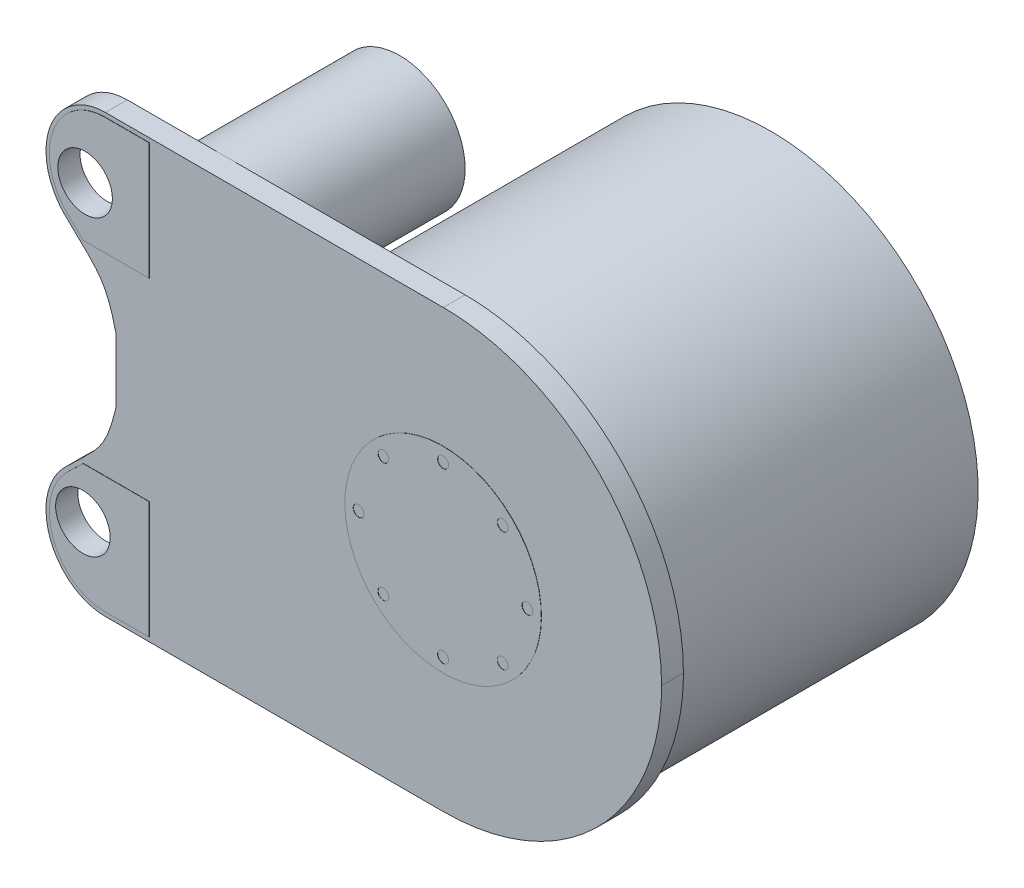
SolidWorks part; units mm, degrees
ref_plane "Plano frontal" through (0, 0, 0) normal (0, 0, 1) x (1, 0, 0)
ref_plane "Plano superior" through (0, 0, 0) normal (0, 1, 0) x (1, 0, 0)
ref_plane "Plano direito" through (0, 0, 0) normal (1, 0, 0) x (0, 0, -1)
sketch "Esboço1" plane through (0, 0, 0) normal (0, 0, 1) x (1, 0, 0)
  line L0 (-10.9, 1.5) -> (-10.9, 1.4998)
  line L1 (-10.9, -1.4998) -> (-10.9, -1.5)
  line L2 (-11.375, -9.9996) -> (-10.1, -9.9996)
  line L3 (-10.1, -9.9996) -> (4.1, -9.9996)
  line L4 (4.1, 9.9996) -> (-10.1, 9.9996)
  line L5 (-10.1, 9.9996) -> (-11.375, 9.9996)
  ellipse E0 centre (4.1, -0.0004) end of major axis (4.1, 9.4996) minor radius 9.5
  ellipse E1 centre (-12.3, 6.7497) end of major axis (-12.3, 7.9997) minor radius 1.25
  ellipse E2 centre (-12.4, -6.7497) end of major axis (-11.15, -6.7497) minor radius 1.2499
  ellipse E5 centre (4.1, -0.0004) end of major axis (4.1, 8.4996) minor radius 8.5
  spline S0 degree 3 poles (-11.375, 9.9996) (-12.8799, 9.9996) (-14.1, 8.7075) (-14.1, 7.1137) knots 0 0 0 0 0.05 0.05 0.05 0.05
  spline S1 degree 3 poles (-14.1, 7.1137) (-14.1, 6.3284) (-13.8037, 5.6164) (-13.3233, 5.0962) knots 0.05 0.05 0.05 0.05 0.1 0.1 0.1 0.1
  spline S2 degree 3 poles (-13.3233, 5.0962) (-13.3196, 5.092) (-13.3154, 5.0875) (-13.3114, 5.0835) knots 0.1 0.1 0.1 0.1 0.15 0.15 0.15 0.15
  spline S3 degree 3 poles (-13.3114, 5.0835) (-13.2765, 5.0461) (-13.2405, 5.0095) (-13.2036, 4.9741) knots 0.15 0.15 0.15 0.15 0.2 0.2 0.2 0.2
  spline S4 degree 3 poles (-13.2036, 4.9741) (-11.7596, 3.5417) (-11.3715, 3.4497) (-10.9, 1.5) knots 0.2 0.2 0.2 0.2 0.25 0.25 0.25 0.25
  spline S5 degree 3 poles (-10.9, 1.4998) (-10.9, 0.5) (-10.9, -0.5) (-10.9, -1.4998) knots 0.3 0.3 0.3 0.3 0.35 0.35 0.35 0.35
  spline S6 degree 3 poles (-10.9, -1.5) (-11.3712, -3.4492) (-11.761, -3.5431) (-13.2036, -4.9741) knots 0.4 0.4 0.4 0.4 0.45 0.45 0.45 0.45
  spline S7 degree 3 poles (-13.2036, -4.9741) (-13.2369, -5.006) (-13.2695, -5.0389) (-13.3011, -5.0725) knots 0.45 0.45 0.45 0.45 0.5 0.5 0.5 0.5
  spline S8 degree 3 poles (-13.3011, -5.0725) (-13.3105, -5.0824) (-13.3196, -5.0921) (-13.3287, -5.1021) knots 0.5 0.5 0.5 0.5 0.55 0.55 0.55 0.55
  spline S9 degree 3 poles (-13.3287, -5.1021) (-13.8059, -5.6217) (-14.1, -6.3313) (-14.1, -7.1137) knots 0.55 0.55 0.55 0.55 0.6 0.6 0.6 0.6
  spline S10 degree 3 poles (-14.1, -7.1137) (-14.1, -8.7075) (-12.8799, -9.9996) (-11.375, -9.9996) knots 0.6 0.6 0.6 0.6 0.65 0.65 0.65 0.65
  spline S11 degree 3 poles (4.1, -9.9996) (9.6228, -9.9996) (14.1, -5.5226) (14.1, 0) knots 0.75 0.75 0.75 0.75 0.8 0.8 0.8 0.8
  spline S12 degree 3 poles (14.1, 0) (14.1, 5.5226) (9.6228, 9.9996) (4.1, 9.9996) knots 0.8 0.8 0.8 0.8 0.85 0.85 0.85 0.85
  point P56 (-6.9, 6.9997)
  ellipse B0 centre (-6.9, 6.9997) end of major axis (-3.9, 6.9997) minor radius 2.9999
  ellipse B1 centre (-6.9, 6.9997) end of major axis (-9.15, 6.9997) minor radius 2.25
sketch_block_instance "Bloco1-1"
sketch_block "Bloco1"
extrude "Ressalto-extrusão1" add sketch "Esboço1" along normal blind 1 contours L4 L5 S0 S1 S2 S3 S4 L0 S5 L1 S6 S7 S8 S9 S10 L2 L3 S11 S12
ref_plane "Plano2" through (0, 0, 1) normal (0, 0, 1) x (1, 0, 0)
sketch "Esboço3" plane through (0, 0, 1) normal (0, 0, 1) x (1, 0, 0)
  line L0 (-12.3882, 4.4299) -> (-9.3652, 4.4299)
  line L1 (-9.3652, 4.4299) -> (-9.3652, 9.8065)
  line L2 (-9.3652, 9.8065) -> (-10.2039, 9.8065)
  line L3 (-10.2039, 9.8065) -> (-11.3935, 9.8065)
  line L4 (-12.3882, -4.4299) -> (-9.3652, -4.4299)
  line L5 (-9.3652, -4.4299) -> (-9.3652, -9.8065)
  line L6 (-9.3652, -9.8065) -> (-10.2039, -9.8065)
  line L7 (-10.2039, -9.8065) -> (-11.3935, -9.8065)
  ellipse E0 centre (4.1, -0.0004) end of major axis (4.1, 4.4996) minor radius 4.5
  ellipse E1 centre (4.1, 3.8664) end of major axis (3.85, 3.8664) minor radius 0.25
  spline S0 degree 3 poles (-11.3935, 9.8065) (-12.7975, 9.8065) (-13.9358, 8.601) (-13.9358, 7.114) knots 0 0 0 0 0.1 0.1 0.1 0.1
  spline S1 degree 3 poles (-13.9358, 7.114) (-13.9358, 6.3813) (-13.6594, 5.717) (-13.2112, 5.2317) knots 0.1 0.1 0.1 0.1 0.2 0.2 0.2 0.2
  spline S2 degree 3 poles (-13.2112, 5.2317) (-13.2077, 5.2278) (-13.2038, 5.2236) (-13.2001, 5.2199) knots 0.2 0.2 0.2 0.2 0.3 0.3 0.3 0.3
  spline S3 degree 3 poles (-13.2001, 5.2199) (-13.1675, 5.185) (-13.1339, 5.1508) (-13.0995, 5.1178) knots 0.3 0.3 0.3 0.3 0.4 0.4 0.4 0.4
  spline S4 degree 3 poles (-13.0995, 5.1178) (-12.8243, 4.8448) (-12.5903, 4.624) (-12.3882, 4.4299) knots 0.4 0.4 0.4 0.4 0.5 0.5 0.5 0.5
  spline S5 degree 3 poles (-11.3935, -9.8065) (-12.7975, -9.8065) (-13.9358, -8.601) (-13.9358, -7.114) knots 0 0 0 0 0.1 0.1 0.1 0.1
  spline S6 degree 3 poles (-13.9358, -7.114) (-13.9358, -6.3813) (-13.6594, -5.717) (-13.2112, -5.2317) knots 0.1 0.1 0.1 0.1 0.2 0.2 0.2 0.2
  spline S7 degree 3 poles (-13.2112, -5.2317) (-13.2077, -5.2278) (-13.2038, -5.2236) (-13.2001, -5.2199) knots 0.2 0.2 0.2 0.2 0.3 0.3 0.3 0.3
  spline S8 degree 3 poles (-13.2001, -5.2199) (-13.1675, -5.185) (-13.1339, -5.1508) (-13.0995, -5.1178) knots 0.3 0.3 0.3 0.3 0.4 0.4 0.4 0.4
  spline S9 degree 3 poles (-13.0995, -5.1178) (-12.8243, -4.8448) (-12.5903, -4.624) (-12.3882, -4.4299) knots 0.4 0.4 0.4 0.4 0.5 0.5 0.5 0.5
  spline S10 degree 3 poles (7.011, 2.9106) (7.1086, 2.813) (7.1086, 2.6547) (7.011, 2.5571) knots 0 0 0 0 0.2 0.2 0.2 0.2
  spline S11 degree 3 poles (7.011, 2.5571) (6.9134, 2.4594) (6.7551, 2.4594) (6.6575, 2.5571) knots 0.2 0.2 0.2 0.2 0.4 0.4 0.4 0.4
  spline S12 degree 3 poles (6.6575, 2.5571) (6.5598, 2.6547) (6.5598, 2.813) (6.6575, 2.9106) knots 0.4 0.4 0.4 0.4 0.6 0.6 0.6 0.6
  spline S13 degree 3 poles (6.6575, 2.9106) (6.7551, 3.0082) (6.9134, 3.0082) (7.011, 2.9106) knots 0.6 0.6 0.6 0.6 1 1 1 1
  spline S14 degree 3 poles (8.2168, -0.0004) (8.2168, -0.1385) (8.1049, -0.2504) (7.9668, -0.2504) knots 0 0 0 0 0.2 0.2 0.2 0.2
  spline S15 degree 3 poles (7.9668, -0.2504) (7.8287, -0.2504) (7.7168, -0.1385) (7.7168, -0.0004) knots 0.2 0.2 0.2 0.2 0.4 0.4 0.4 0.4
  spline S16 degree 3 poles (7.7168, -0.0004) (7.7168, 0.1377) (7.8287, 0.2496) (7.9668, 0.2496) knots 0.4 0.4 0.4 0.4 0.6 0.6 0.6 0.6
  spline S17 degree 3 poles (7.9668, 0.2496) (8.1049, 0.2496) (8.2168, 0.1377) (8.2168, -0.0004) knots 0.6 0.6 0.6 0.6 1 1 1 1
  spline S18 degree 3 poles (7.011, -2.9114) (6.9134, -3.009) (6.7551, -3.009) (6.6575, -2.9114) knots 0 0 0 0 0.2 0.2 0.2 0.2
  spline S19 degree 3 poles (6.6575, -2.9114) (6.5598, -2.8138) (6.5598, -2.6555) (6.6575, -2.5579) knots 0.2 0.2 0.2 0.2 0.4 0.4 0.4 0.4
  spline S20 degree 3 poles (6.6575, -2.5579) (6.7551, -2.4602) (6.9134, -2.4602) (7.011, -2.5579) knots 0.4 0.4 0.4 0.4 0.6 0.6 0.6 0.6
  spline S21 degree 3 poles (7.011, -2.5579) (7.1086, -2.6555) (7.1086, -2.8138) (7.011, -2.9114) knots 0.6 0.6 0.6 0.6 1 1 1 1
  spline S22 degree 3 poles (4.1, -4.1172) (3.9619, -4.1172) (3.85, -4.0053) (3.85, -3.8672) knots 0 0 0 0 0.2 0.2 0.2 0.2
  spline S23 degree 3 poles (3.85, -3.8672) (3.85, -3.7291) (3.9619, -3.6172) (4.1, -3.6172) knots 0.2 0.2 0.2 0.2 0.4 0.4 0.4 0.4
  spline S24 degree 3 poles (4.1, -3.6172) (4.2381, -3.6172) (4.35, -3.7291) (4.35, -3.8672) knots 0.4 0.4 0.4 0.4 0.6 0.6 0.6 0.6
  spline S25 degree 3 poles (4.35, -3.8672) (4.35, -4.0053) (4.2381, -4.1172) (4.1, -4.1172) knots 0.6 0.6 0.6 0.6 1 1 1 1
  spline S26 degree 3 poles (1.189, -2.9114) (1.0914, -2.8138) (1.0914, -2.6555) (1.189, -2.5579) knots 0 0 0 0 0.2 0.2 0.2 0.2
  spline S27 degree 3 poles (1.189, -2.5579) (1.2866, -2.4602) (1.4449, -2.4602) (1.5425, -2.5579) knots 0.2 0.2 0.2 0.2 0.4 0.4 0.4 0.4
  spline S28 degree 3 poles (1.5425, -2.5579) (1.6402, -2.6555) (1.6402, -2.8138) (1.5425, -2.9114) knots 0.4 0.4 0.4 0.4 0.6 0.6 0.6 0.6
  spline S29 degree 3 poles (1.5425, -2.9114) (1.4449, -3.009) (1.2866, -3.009) (1.189, -2.9114) knots 0.6 0.6 0.6 0.6 1 1 1 1
  spline S30 degree 3 poles (-0.0168, -0.0004) (-0.0168, 0.1377) (0.0951, 0.2496) (0.2332, 0.2496) knots 0 0 0 0 0.2 0.2 0.2 0.2
  spline S31 degree 3 poles (0.2332, 0.2496) (0.3713, 0.2496) (0.4832, 0.1377) (0.4832, -0.0004) knots 0.2 0.2 0.2 0.2 0.4 0.4 0.4 0.4
  spline S32 degree 3 poles (0.4832, -0.0004) (0.4832, -0.1385) (0.3713, -0.2504) (0.2332, -0.2504) knots 0.4 0.4 0.4 0.4 0.6 0.6 0.6 0.6
  spline S33 degree 3 poles (0.2332, -0.2504) (0.0951, -0.2504) (-0.0168, -0.1385) (-0.0168, -0.0004) knots 0.6 0.6 0.6 0.6 1 1 1 1
  spline S34 degree 3 poles (1.189, 2.9106) (1.2866, 3.0082) (1.4449, 3.0082) (1.5425, 2.9106) knots 0 0 0 0 0.2 0.2 0.2 0.2
  spline S35 degree 3 poles (1.5425, 2.9106) (1.6402, 2.813) (1.6402, 2.6547) (1.5425, 2.5571) knots 0.2 0.2 0.2 0.2 0.4 0.4 0.4 0.4
  spline S36 degree 3 poles (1.5425, 2.5571) (1.4449, 2.4594) (1.2866, 2.4594) (1.189, 2.5571) knots 0.4 0.4 0.4 0.4 0.6 0.6 0.6 0.6
  spline S37 degree 3 poles (1.189, 2.5571) (1.0914, 2.6547) (1.0914, 2.813) (1.189, 2.9106) knots 0.6 0.6 0.6 0.6 1 1 1 1
extrude "Ressalto-extrusão8" add sketch "Esboço3" along normal blind 0.01
extrude "Corte-extrusão1" cut sketch "Esboço1<3>" along normal blind 1.5 contours E1 | E2
sketch "Esboço1<3>" plane through (0, 0, 0) normal (0, 0, 1) x (1, 0, 0) same geometry as "Esboço1"
extrude "Ressalto-extrusão2" add sketch "Esboço1<4>" against normal blind 14 contours E0 | E5
sketch "Esboço1<4>" plane through (0, 0, 0) normal (0, 0, 1) x (1, 0, 0) same geometry as "Esboço1"
extrude "Ressalto-extrusão3" add sketch "Esboço1<5>" against normal blind 8 contours B0 | B1
sketch "Esboço1<5>" plane through (0, 0, 0) normal (0, 0, 1) x (1, 0, 0) same geometry as "Esboço1"
extrude "Ressalto-extrusão4" add sketch "Esboço1<6>" against normal blind 11.5 contours E5
sketch "Esboço1<6>" plane through (0, 0, 0) normal (0, 0, 1) x (1, 0, 0) same geometry as "Esboço1"
extrude "Ressalto-extrusão5" add sketch "Esboço1<7>" against normal blind 6.5 contours B1
sketch "Esboço1<7>" plane through (0, 0, 0) normal (0, 0, 1) x (1, 0, 0) same geometry as "Esboço1"
sketch "Esboço4" plane through (0, 0, 0) normal (0, 0, 1) x (1, 0, 0)
  line L0 (-12.3882, 4.4299) -> (-9.3652, 4.4299)
  line L1 (-9.3652, 4.4299) -> (-9.3652, 9.8065)
  line L2 (-9.3652, 9.8065) -> (-10.2039, 9.8065)
  line L3 (-10.2039, 9.8065) -> (-11.3935, 9.8065)
  line L4 (-12.3882, -4.4299) -> (-9.3652, -4.4299)
  line L5 (-9.3652, -4.4299) -> (-9.3652, -9.8065)
  line L6 (-9.3652, -9.8065) -> (-10.2039, -9.8065)
  line L7 (-10.2039, -9.8065) -> (-11.3935, -9.8065)
  spline S0 degree 3 poles (-11.3935, 9.8065) (-12.7975, 9.8065) (-13.9358, 8.601) (-13.9358, 7.114) knots 0 0 0 0 0.1 0.1 0.1 0.1
  spline S1 degree 3 poles (-13.9358, 7.114) (-13.9358, 6.3813) (-13.6594, 5.717) (-13.2112, 5.2317) knots 0.1 0.1 0.1 0.1 0.2 0.2 0.2 0.2
  spline S2 degree 3 poles (-13.2112, 5.2317) (-13.2077, 5.2278) (-13.2038, 5.2236) (-13.2001, 5.2199) knots 0.2 0.2 0.2 0.2 0.3 0.3 0.3 0.3
  spline S3 degree 3 poles (-13.2001, 5.2199) (-13.1675, 5.185) (-13.1339, 5.1508) (-13.0995, 5.1178) knots 0.3 0.3 0.3 0.3 0.4 0.4 0.4 0.4
  spline S4 degree 3 poles (-13.0995, 5.1178) (-12.8243, 4.8448) (-12.5903, 4.624) (-12.3882, 4.4299) knots 0.4 0.4 0.4 0.4 0.5 0.5 0.5 0.5
  spline S5 degree 3 poles (-11.3935, -9.8065) (-12.7975, -9.8065) (-13.9358, -8.601) (-13.9358, -7.114) knots 0 0 0 0 0.1 0.1 0.1 0.1
  spline S6 degree 3 poles (-13.9358, -7.114) (-13.9358, -6.3813) (-13.6594, -5.717) (-13.2112, -5.2317) knots 0.1 0.1 0.1 0.1 0.2 0.2 0.2 0.2
  spline S7 degree 3 poles (-13.2112, -5.2317) (-13.2077, -5.2278) (-13.2038, -5.2236) (-13.2001, -5.2199) knots 0.2 0.2 0.2 0.2 0.3 0.3 0.3 0.3
  spline S8 degree 3 poles (-13.2001, -5.2199) (-13.1675, -5.185) (-13.1339, -5.1508) (-13.0995, -5.1178) knots 0.3 0.3 0.3 0.3 0.4 0.4 0.4 0.4
  spline S9 degree 3 poles (-13.0995, -5.1178) (-12.8243, -4.8448) (-12.5903, -4.624) (-12.3882, -4.4299) knots 0.4 0.4 0.4 0.4 0.5 0.5 0.5 0.5
extrude "Ressalto-extrusão11" add sketch "Esboço4" against normal blind 0.01
extrude "Corte-extrusão4" cut sketch "Esboço1<9>" against normal blind 0.5 contours E1 | E2
sketch "Esboço1<9>" plane through (0, 0, 0) normal (0, 0, 1) x (1, 0, 0) same geometry as "Esboço1"
